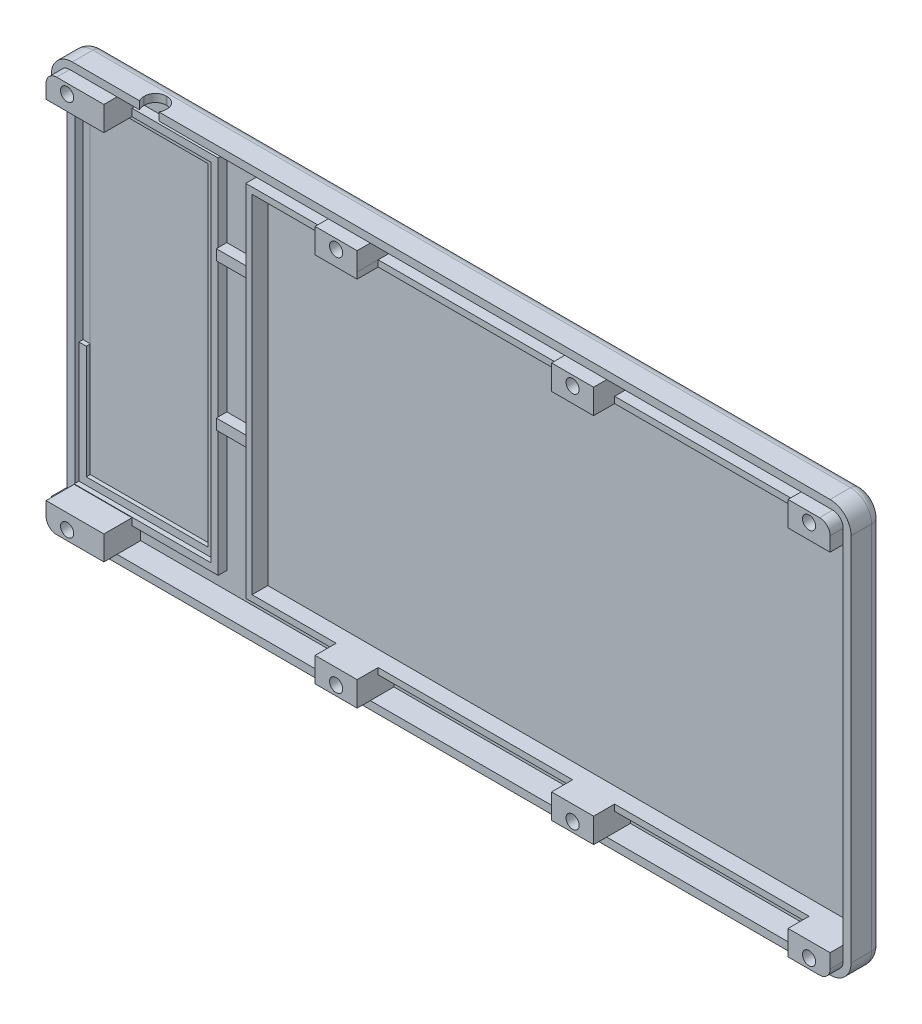
SolidWorks part; units mm, degrees
ref_plane "Plan de face" through (0, 0, 0) normal (0, 0, 1) x (1, 0, 0)
ref_plane "Plan de dessus" through (0, 0, 0) normal (0, 1, 0) x (1, 0, 0)
ref_plane "Plan de droite" through (0, 0, 0) normal (1, 0, 0) x (0, 0, -1)
sketch "Esquisse1" plane through (0, 0, 0) normal (0, 0, 1) x (1, 0, 0)
  line L0 (149.2, 71.9) -> (34, 71.9)
  line L1 (0, 0) -> (147.2, 0)
  line L2 (0, 0) -> (0, 75.4)
  line L3 (0, 75.4) -> (147.2, 75.4)
  line L4 (149.2, 2) -> (149.2, 73.4)
  line L5 (34, 71.9) -> (34, 3.5)
  line L6 (34, 3.5) -> (149.2, 3.5)
  line L7 (149.2, 70.7) -> (35.2, 70.7)
  line L8 (35.2, 70.7) -> (35.2, 4.7)
  line L9 (35.2, 4.7) -> (149.2, 4.7)
  line L10 (-19.055, 37.7) -> (204.5006, 37.7) construction
  line L11 (-1.5, 76.9) -> (150.7, 76.9)
  line L12 (-1.5, 76.9) -> (-1.5, -1.5)
  line L13 (-1.5, -1.5) -> (150.7, -1.5)
  line L14 (150.7, 76.9) -> (150.7, -1.5)
  line L15 (0, 72.1) -> (0, 70.7)
  line L16 (26, 70.7) -> (0, 70.7)
  line L17 (26, 70.7) -> (26, 4.7)
  line L18 (26, 4.7) -> (0, 4.7)
  line L19 (0, 70.7) -> (0, 4.7)
  line L20 (1.4, 69.3) -> (24.6, 69.3)
  line L21 (1.4, 69.3) -> (1.4, 6.1)
  line L22 (1.4, 6.1) -> (24.6, 6.1)
  line L23 (24.6, 69.3) -> (24.6, 6.1)
  line L24 (0, 72.1) -> (27.4, 72.1)
  line L25 (0, 3.3) -> (0, 4.7)
  line L26 (0, 3.3) -> (27.4, 3.3)
  line L27 (27.4, 72.1) -> (27.4, 3.3)
  line L28 (141.2, 75.4) -> (141.2, 71.9)
  line L30 (96.2, 75.4) -> (96.2, 71.9)
  line L31 (104.2, 75.4) -> (104.2, 71.9)
  line L32 (51.2, 75.4) -> (51.2, 71.9)
  line L33 (59.2, 75.4) -> (59.2, 71.9)
  line L35 (141.2, 0) -> (141.2, 3.5)
  line L36 (104.2, 0) -> (104.2, 3.5)
  line L37 (96.2, 0) -> (96.2, 3.5)
  line L38 (59.2, 0) -> (59.2, 3.5)
  line L39 (51.2, 0) -> (51.2, 3.5)
  circle A0 centre (145.2, 73.6) radius 1.25
  arc A1 (147.2, 75.4) -> (149.2, 73.4) centre (147.2, 73.4) cw
  arc A2 (147.2, 0) -> (149.2, 2) centre (147.2, 2) ccw
  circle A3 centre (100.2, 73.6) radius 1.25
  circle A5 centre (55.2, 73.6) radius 1.25
  circle A6 centre (145.2, 1.8) radius 1.25
  circle A8 centre (100.2, 1.8) radius 1.25
  circle A11 centre (55.2, 1.8) radius 1.25
  dimension "D12" = 2.5
  dimension "D13" = 3.5
  dimension "D40" = 2
  dimension "D1" = 1.5
  dimension "D3" = 1.2
  dimension "D4" = 1.2
  dimension "D5" = 1.2
  dimension "D6" = 66
  dimension "D7" = 3.5
  dimension "D8" = 114
  dimension "D9" = 1.5
  dimension "D10" = 1.5
  dimension "D11" = 1.5
  dimension "D15" = 33
  dimension "D16" = 33
  dimension "D17" = 1.8
  dimension "D18" = 66
  dimension "D19" = 26
  dimension "D20" = 33
  dimension "D21" = 33
  dimension "D22" = 8
  dimension "D23" = 1.4
  dimension "D24" = 1.4
  dimension "D25" = 1.4
  dimension "D26" = 1.4
  dimension "D27" = 1.4
  dimension "D28" = 0
  dimension "D29" = 1.4
  dimension "D30" = 1.4
  dimension "D31" = 4
  dimension "D32" = 0
  dimension "D33" = 0
  dimension "D34" = 4
  dimension "D35" = 45
  dimension "D36" = 4
  dimension "D37" = 4
  dimension "D38" = 4
  dimension "D39" = 4
  dimension "D14" = 3
extrude "Boss.-Extru.1" add sketch "Esquisse1" along normal blind 5.9 contours L12 L10 L2 L3 L4 L14 L11 | L10 L12 L13 L14 L4 L1 L2 region at (149.3572, 72.65, 0) region at (149.95, 36.1283, 0)
extrude "Boss.-Extru.2" add sketch "Esquisse1<4>" along normal blind 1.4 contours L3 A1 L4 A2 L1 L2
sketch "Esquisse1<4>" plane through (0, 0, 0) normal (0, 0, 1) x (1, 0, 0) same geometry as "Esquisse1"
extrude "Boss.-Extru.5" add sketch "Esquisse1<5>" along normal blind 7 from surface separate body contours A5 | A3 | A0 | A11 | A8 | A6 region at (145.2, 71.9873, 0) region at (100.2, 71.9873, 0) region at (149.1127, 2.75, 0) region at (55.2, 71.9873, 0) region at (104.1127, 1.75, 0) region at (59.1127, 1.75, 0) starting at face at (98.9381, 37.7, 1.4)
sketch "Esquisse1<5>" plane through (0, 0, 0) normal (0, 0, 1) x (1, 0, 0) same geometry as "Esquisse1"
extrude "Boss.-Extru.7" add sketch "Esquisse1<6>" along normal blind 3 from surface contours L5 L10 L8 L7 L4 L0 | L10 L5 L6 L4 L9 L8 region at (147.9983, 71.3, 0) region at (147.9983, 4.1, 0) starting at face at (98.9381, 37.7, 1.4)
sketch "Esquisse1<6>" plane through (0, 0, 0) normal (0, 0, 1) x (1, 0, 0) same geometry as "Esquisse1"
fillet "Congé1" radius 4 4 edges at (-1.5, 76.9, 2.95) (-1.5, -1.5, 2.95) (150.7, -1.5, 2.95) (150.7, 76.9, 2.95)
fillet "Congé4" radius 2 2 edges at (0, 0, 3.65) (0, 75.4, 3.65)
extrude "Boss.-Extru.8" add sketch "Esquisse1<7>" along normal blind 0.75 from surface contours L19 L10 L21 L20 L23 L17 L16 | L10 L19 L18 L17 L23 L22 L21 region at (25.5799, 21.2, 0) region at (25.3, 38.1201, 0) starting at face at (80.2667, 37.7, 1.4)
sketch "Esquisse1<7>" plane through (0, 0, 0) normal (0, 0, 1) x (1, 0, 0) same geometry as "Esquisse1"
extrude "Boss.-Extru.9" add sketch "Esquisse1<8>" along normal blind 1.65 from surface contours L10 L26 L27 L17 L18 L19 | L10 L19 L16 L17 L27 L24 region at (26.9602, 20.5, 0) region at (26.7, 38.1398, 0) starting at face at (63.45, 37.7, 1.4)
sketch "Esquisse1<8>" plane through (0, 0, 0) normal (0, 0, 1) x (1, 0, 0) same geometry as "Esquisse1"
sketch "Esquisse2" plane through (0, 0, 5.9) normal (0, 0, 1) x (1, 0, 0)
  line L0 (-1.5, 72.9) -> (-1.5, 2.5) construction
  line L1 (0, 72.1) -> (-1.5, 72.1)
  line L2 (0, 72.1) -> (0, 3.3)
  line L3 (0, 3.3) -> (-1.5, 3.3)
  line L4 (-1.5, 72.1) -> (-1.5, 3.3)
  line L5 (0, 3.3) -> (27.4, 3.3) construction
  dimension "D1" = 0
sketch "Esquisse4" plane through (0, 0, 1.4) normal (0, 0, 1) x (1, 0, 0)
  line L1 (2, 0) -> (147.2, 0) construction
  line L2 (2, 75.4) -> (147.2, 75.4) construction
  line L5 (11, 75.4) -> (2, 75.4)
  line L6 (11, 75.4) -> (11, 70.7374)
  line L7 (11, 70.7374) -> (0, 70.7374)
  line L8 (0, 73.4) -> (0, 70.7374)
  line L9 (0, 4.6081) -> (11, 4.6081)
  line L10 (0, 4.6081) -> (0, 2)
  line L11 (2, 0) -> (11, 0)
  line L12 (11, 4.6081) -> (11, 0)
  circle A0 centre (4, 1.8) radius 1.25
  circle A1 centre (4, 73.6) radius 1.25
  circle A2 centre (55.2, 1.8) radius 1.25 construction
  circle A3 centre (55.2, 73.6) radius 1.25 construction
  arc A4 (0, 2) -> (2, 0) centre (2, 2) ccw
  arc A5 (2, 75.4) -> (0, 73.4) centre (2, 73.4) ccw
  dimension "D1" = 2.5
  dimension "D4" = 2.5
  dimension "D9" = 2
  dimension "D2" = 7
  dimension "D3" = 0
  dimension "D5" = 0
  dimension "D6" = 7
  dimension "D7" = 11
  dimension "D8" = 11
extrude "Boss.-Extru.11" add sketch "Esquisse4" along normal blind 7
sketch "Esquisse5" plane through (0, 0, 1.4) normal (0, 0, 1) x (1, 0, 0)
  line L16 (34, 71.9) -> (34, 3.5) construction
  line L21 (34, 57.3296) -> (27.4, 57.3296)
  line L22 (34, 57.3296) -> (34, 55.3296)
  line L23 (34, 55.3296) -> (27.4, 55.3296)
  line L24 (27.4, 57.3296) -> (27.4, 55.3296)
  line L25 (27.4, 72.1) -> (27.4, 3.3) construction
  line L26 (27.4, 72.1) -> (27.4, 3.3) construction
  line L27 (34, 29.422) -> (27.4, 29.422)
  line L28 (34, 29.422) -> (34, 27.422)
  line L29 (34, 27.422) -> (27.4, 27.422)
  line L30 (27.4, 29.422) -> (27.4, 27.422)
  dimension "D3" = 2
  dimension "D4" = 2
extrude "Boss.-Extru.12" add sketch "Esquisse5" along normal blind 2
fillet "Congé3" radius 2 8 edges at (-0.3284, -0.3284, 0) (-1.5, 37.7, 0) (-0.3284, 75.7284, 0) (74.6, 76.9, 0) (149.5284, 75.7284, 0) (150.7, 37.7, 0) (149.5284, -0.3284, 0) (74.6, -1.5, 0)
extrude "Enlèv. mat.-Extru.1" cut sketch "Esquisse2" against normal blind 3
sketch "Esquisse6" plane through (0, 76.9, 0) normal (0, 1, 0) x (1, 0, 0)
  line L1 (17, -2.5955) -> (17.25, -2.5955)
  line L2 (15, -4.5955) -> (15, -4.8455)
  line L3 (17, -6.8455) -> (17.25, -6.8455)
  line L4 (19.25, -4.5955) -> (19.25, -4.8455)
  line L7 (2.5, -2) -> (2.5, -5.9) construction
  arc A0 (15, -4.8455) -> (17, -6.8455) centre (17, -4.8455) ccw
  arc A1 (17.25, -6.8455) -> (19.25, -4.8455) centre (17.25, -4.8455) ccw
  arc A2 (17.25, -2.5955) -> (19.25, -4.5955) centre (17.25, -4.5955) cw
  arc A3 (17, -2.5955) -> (15, -4.5955) centre (17, -4.5955) ccw
  point P8 (15, -6.8455)
  point P13 (19.25, -2.5955)
  point P16 (15, -2.5955)
  dimension "D4" = 2
  dimension "D1" = 4.25
  dimension "D2" = 4.25
  dimension "D3" = 12.5
extrude "Enlèv. mat.-Extru.2" cut sketch "Esquisse6" against normal blind 1.5
sketch "Esquisse7" plane through (0, 0, 2.15) normal (0, 0, 1) x (1, 0, 0)
  line L0 (0, 4.7) -> (0, 70.7) construction
  line L1 (1.4, 69.3) -> (0, 69.3)
  line L2 (1.4, 69.3) -> (1.4, 27.6196)
  line L3 (1.4, 27.6196) -> (0, 27.6196)
  line L4 (0, 69.3) -> (0, 27.6196)
extrude "Enlèv. mat.-Extru.3" cut sketch "Esquisse7" against normal blind 0.8
sketch "Esquisse8" plane through (0, 0, 4.4) normal (0, 0, 1) x (1, 0, 0)
  line L0 (149.2, 70.7) -> (35.2, 70.7) construction
  line L1 (51.2, 71.9) -> (59.1967, 71.9)
  line L2 (51.2, 71.9) -> (51.2, 70.7)
  line L3 (51.2, 70.7) -> (59.1967, 70.7)
  line L4 (59.1967, 71.9) -> (59.1967, 70.7)
  line L5 (35.2, 4.7) -> (149.2, 4.7) construction
  line L6 (104.2, 71.9) -> (96.1992, 71.9)
  line L7 (104.2, 71.9) -> (104.2, 70.7)
  line L8 (104.2, 70.7) -> (96.1992, 70.7)
  line L9 (96.1992, 71.9) -> (96.1992, 70.7)
  line L10 (141.2, 71.9) -> (149.2, 71.9)
  line L11 (141.2, 71.9) -> (141.2, 70.7)
  line L12 (141.2, 70.7) -> (149.2, 70.7)
  line L13 (149.2, 71.9) -> (149.2, 70.7)
  line L14 (149.2, 3.5) -> (141.2, 3.5)
  line L15 (149.2, 3.5) -> (149.2, 4.7)
  line L16 (149.2, 4.7) -> (141.2, 4.7)
  line L17 (141.2, 3.5) -> (141.2, 4.7)
  line L18 (35.2, 4.7) -> (149.2, 4.7) construction
  line L19 (104.2, 3.5) -> (96.1992, 3.5)
  line L20 (104.2, 3.5) -> (104.2, 4.7)
  line L21 (104.2, 4.7) -> (96.1992, 4.7)
  line L22 (96.1992, 3.5) -> (96.1992, 4.7)
  line L23 (59.2, 3.5) -> (51.2, 3.5)
  line L24 (59.2, 3.5) -> (59.2, 4.7)
  line L25 (59.2, 4.7) -> (51.2, 4.7)
  line L26 (51.2, 3.5) -> (51.2, 4.7)
extrude "Boss.-Extru.13" add sketch "Esquisse8" along normal blind 4
